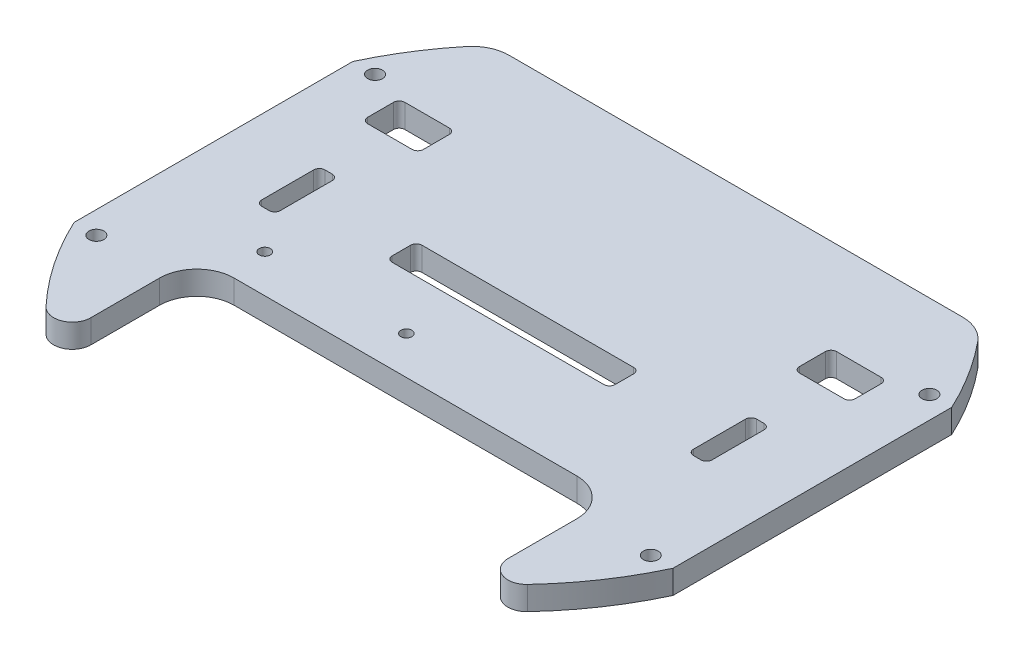
SolidWorks part; units mm, degrees
ref_plane "Front Plane" through (0, 0, 0) normal (0, 0, 1) x (1, 0, 0)
ref_plane "Top Plane" through (0, 0, 0) normal (0, 1, 0) x (1, 0, 0)
ref_plane "Right Plane" through (0, 0, 0) normal (1, 0, 0) x (0, 0, -1)
sketch "Sketch1" plane through (0, 0, 0) normal (0, 1, 0) x (1, 0, 0)
  line L0 (-80.6037, 37.5) -> (-80.6037, -37.5)
  line L1 (0, -88.9) -> (0, 88.9) construction
  line L2 (80.6037, 37.5) -> (80.6037, -37.5)
  arc A0 (-80.6037, -37.5) -> (80.6037, -37.5) centre (0, 0) ccw
  arc A1 (80.6037, 37.5) -> (-80.6037, 37.5) centre (0, 0) ccw
  dimension "D1" = 177.8
  dimension "D2" = 75
extrude "Main Body" add sketch "Sketch1" along normal blind 6.35
sketch "Sketch2" plane through (0, 6.35, 0) normal (0, 1, 0) x (1, 0, 0)
  line L0 (0, 88.9) -> (0, -88.9) construction
  line L1 (36.5, 69.85) -> (-21.5, 69.85) construction
  line L2 (36.5, 69.85) -> (36.5, 20.85) construction
  line L3 (36.5, 20.85) -> (-21.5, 20.85) construction
  line L4 (-21.5, 69.85) -> (-21.5, 20.85) construction
  line L5 (36.5, 69.85) -> (-21.5, 20.85) construction
  line L6 (36.5, 20.85) -> (-21.5, 69.85) construction
  line L7 (32.5, 20.85) -> (32.5, 69.85) construction
  line L8 (-25.5, 20.85) -> (-25.5, 69.85) construction
  circle A0 centre (36.5, 69.85) radius 1.524
  circle A1 centre (36.5, 20.85) radius 1.524
  circle A2 centre (-21.5, 20.85) radius 1.524
  circle A3 centre (-21.5, 69.85) radius 1.524
  arc A4 (-80.6037, -37.5) -> (80.6037, -37.5) centre (0, 0) ccw construction
  arc A5 (80.6037, 37.5) -> (-80.6037, 37.5) centre (0, 0) ccw construction
  circle A6 centre (32.5, 20.85) radius 1.1
  circle A7 centre (-25.5, 20.85) radius 1.1
  circle A8 centre (32.5, 69.85) radius 1.1
  circle A9 centre (-25.5, 69.85) radius 1.1
  point P0 (7.5, 45.35)
  point P11 (0, 88.9)
  dimension "D3" = 3.048
  dimension "D6" = 2.2
  dimension "D1" = 58
  dimension "D2" = 49
  dimension "D4" = 19.05
  dimension "D5" = 15
  dimension "D7" = 4
  dimension "D8" = 4
sketch "Sketch3" plane through (0, 6.35, 0) normal (0, 1, 0) x (1, 0, 0)
  line L0 (-80.6037, 0) -> (80.6037, 0) construction
  line L1 (-80.6037, 37.5) -> (-80.6037, -37.5) construction
  line L2 (80.6037, -37.5) -> (80.6037, 37.5) construction
  line L3 (-74.3537, -9) -> (-74.3537, 9) construction
  line L4 (0, -88.9) -> (0, 88.9) construction
  line L5 (74.3537, -9) -> (74.3537, 9) construction
  circle A0 centre (-74.3537, 9) radius 1.143
  circle A1 centre (-74.3537, -9) radius 1.143
  arc A2 (-80.6037, -37.5) -> (80.6037, -37.5) centre (0, 0) ccw construction
  arc A3 (80.6037, 37.5) -> (-80.6037, 37.5) centre (0, 0) ccw construction
  circle A4 centre (74.3537, 9) radius 1.143
  circle A5 centre (74.3537, -9) radius 1.143
  point P10 (-74.3537, 0)
  point P19 (74.3537, 0)
  dimension "D1" = 6.25
  dimension "D2" = 2.286
  dimension "D3" = 18
sketch "Sketch4" plane through (0, 6.35, 0) normal (0, 1, 0) x (1, 0, 0)
  line L0 (0, -88.9) -> (0, 88.9) construction
  line L1 (-7.747, 78.9) -> (7.747, 78.9) construction
  arc A0 (-80.6037, -37.5) -> (80.6037, -37.5) centre (0, 0) ccw construction
  arc A1 (80.6037, 37.5) -> (-80.6037, 37.5) centre (0, 0) ccw construction
  circle A2 centre (-7.747, 78.9) radius 1.524
  circle A3 centre (7.747, 78.9) radius 1.524
  point P10 (0, 78.9)
  dimension "D1" = 3.048
  dimension "D2" = 15.494
  dimension "D3" = 10
sketch "Sketch5" plane through (0, 6.35, 0) normal (0, 1, 0) x (1, 0, 0)
  line L0 (0, -88.9) -> (0, 88.9) construction
  line L1 (29.21, -82.5485) -> (29.21, 0.1133) construction
  line L2 (29.21, -24.4861) -> (50029.21, -24.4861) construction
  line L3 (29.21, -28.2961) -> (56.134, -28.2961) construction
  line L4 (29.21, -28.2961) -> (29.21, -68.9361) construction
  line L5 (29.21, -68.9361) -> (56.134, -68.9361) construction
  line L6 (56.134, -28.2961) -> (56.134, -68.9361) construction
  line L7 (29.21, -72.7461) -> (50029.21, -72.7461) construction
  line L8 (29.21, -28.2961) -> (29.21, -24.4861) construction
  line L9 (29.21, -68.9361) -> (29.21, -72.7461) construction
  line L10 (35.56, -24.4861) -> (35.56, -72.7461) construction
  arc A0 (-80.6037, -37.5) -> (80.6037, -37.5) centre (0, 0) ccw construction
  arc A1 (80.6037, 37.5) -> (-80.6037, 37.5) centre (0, 0) ccw construction
  circle A2 centre (35.56, -24.4861) radius 1.524
  circle A3 centre (35.56, -72.7461) radius 1.524
  dimension "D4" = 3.048
  dimension "D1" = 29.21
  dimension "D2" = 40.64
  dimension "D3" = 26.924
  dimension "D5" = 6.35
  dimension "D6" = 48.26
sketch "Sketch6" plane through (0, 6.35, 0) normal (0, 1, 0) x (1, 0, 0)
  line L0 (0, -88.1692) -> (0, -5.66) construction
  line L2 (-26.543, -75.692) -> (26.543, -75.692) construction
  line L3 (-26.543, -75.692) -> (-26.543, -63.5) construction
  line L4 (-26.543, -63.5) -> (26.543, -63.5) construction
  line L5 (26.543, -75.692) -> (26.543, -63.5) construction
  line L6 (-26.543, -75.692) -> (26.543, -63.5) construction
  line L7 (-26.543, -63.5) -> (26.543, -75.692) construction
  circle A0 centre (-12.7, -69.596) radius 1.524
  circle A1 centre (12.7, -69.596) radius 1.524
  point P1 (0, -69.596)
  dimension "D4" = 3.048
  dimension "D1" = 63.5
  dimension "D2" = 12.192
  dimension "D3" = 53.086
  dimension "D5" = 25.4
  dimension "D6" = 12.7
extrude "Front IR" cut sketch "Sketch6" against normal through all
sketch "Sketch8" plane through (0, 6.35, 0) normal (0, 1, 0) x (1, 0, 0)
  line L0 (0, 0) -> (0, 88.9) construction
  line L1 (-80.6037, 37.5) -> (-80.6037, -37.5) construction
  line L2 (-80.6037, -29.88) -> (80.6037, -29.88) construction
  line L3 (80.6037, -37.5) -> (80.6037, 37.5) construction
  line L4 (-80.6037, 23.206) -> (80.6037, 23.206) construction
  line L5 (0, 23.206) -> (0, -29.88) construction
  line L6 (0, -29.88) -> (0, -3.337) construction
  line L7 (-63.5, -37.5) -> (63.5, -37.5) construction
  circle A1 centre (-63.5, -37.5) radius 1.524
  circle A2 centre (-63.5, -50.2) radius 1.524
  circle A3 centre (63.5, -50.2) radius 1.524
  circle A4 centre (63.5, -37.5) radius 1.524
  dimension "D3" = 3.048
  dimension "D1" = 53.086
  dimension "D2" = 7.62
  dimension "D4" = 12.7
  dimension "D5" = 63.5
  dimension "D6" = 7.62
sketch "Sketch10" plane through (0, 6.35, 0) normal (0, 1, 0) x (1, 0, 0)
  line L0 (0, -88.9) -> (0, 0) construction
  line L1 (19.05, -101.854) -> (19.05, -75.946)
  line L2 (19.05, -101.854) -> (-19.05, -101.854)
  line L3 (19.05, -75.946) -> (-19.05, -75.946)
  line L4 (-19.05, -101.854) -> (-19.05, -75.946)
  line L5 (19.05, -101.854) -> (-19.05, -75.946) construction
  line L6 (19.05, -75.946) -> (-19.05, -101.854) construction
  arc A0 (-80.6037, -37.5) -> (80.6037, -37.5) centre (0, 0) ccw construction
  circle A1 centre (-12.7, -69.596) radius 1.524 construction
  dimension "D2" = 6.35
  dimension "D1" = 38.1
extrude "Grabber slot" cut sketch "Sketch10" against normal through all
sketch "Sketch11" plane through (0, 6.35, 0) normal (0, 1, 0) x (1, 0, 0)
  line L0 (0, 88.9) -> (0, -75.946) construction
  line L1 (19.05, -75.946) -> (-19.05, -75.946) construction
  line L2 (80.6037, 0) -> (-80.6037, 0) construction
  line L3 (80.6037, -37.5) -> (80.6037, 37.5) construction
  line L4 (-80.6037, 37.5) -> (-80.6037, -37.5) construction
  line L5 (-60.6037, 8.5) -> (-55.6037, 8.5)
  line L6 (30, -4) -> (-30, -4)
  line L7 (30, -4) -> (30, 4)
  line L8 (30, 4) -> (-30, 4)
  line L9 (-30, -4) -> (-30, 4)
  line L10 (30, -4) -> (-30, 4) construction
  line L11 (30, 4) -> (-30, -4) construction
  line L12 (60.6037, -8.5) -> (55.6037, -8.5)
  line L13 (60.6037, -8.5) -> (60.6037, 8.5)
  line L14 (60.6037, 8.5) -> (55.6037, 8.5)
  line L15 (55.6037, -8.5) -> (55.6037, 8.5)
  line L16 (60.6037, -8.5) -> (55.6037, 8.5) construction
  line L17 (60.6037, 8.5) -> (55.6037, -8.5) construction
  line L18 (-55.6037, -8.5) -> (-55.6037, 8.5)
  line L19 (-60.6037, -8.5) -> (-55.6037, -8.5)
  line L20 (-60.6037, -8.5) -> (-60.6037, 8.5)
  line L21 (-58.1037, 8.5) -> (-58.1037, 67.2842) construction
  line L22 (58.1037, 8.5) -> (58.1037, 67.2842) construction
  line L23 (50.6037, 35) -> (50.6037, 25)
  line L24 (-65.6037, 35) -> (-50.6037, 35)
  line L25 (-65.6037, 35) -> (-65.6037, 25)
  line L26 (-65.6037, 25) -> (-50.6037, 25)
  line L27 (-50.6037, 35) -> (-50.6037, 25)
  line L28 (-65.6037, 35) -> (-50.6037, 25) construction
  line L29 (-65.6037, 25) -> (-50.6037, 35) construction
  line L30 (65.6037, 35) -> (50.6037, 35)
  line L31 (65.6037, 35) -> (65.6037, 25)
  line L32 (65.6037, 25) -> (50.6037, 25)
  arc A0 (80.6037, 37.5) -> (-80.6037, 37.5) centre (0, 0) ccw construction
  point P13 (0, 0)
  point P19 (58.1037, 0)
  point P32 (-58.1037, 30)
  dimension "D3" = 20
  dimension "D1" = 8
  dimension "D2" = 60
  dimension "D4" = 17
  dimension "D5" = 5
  dimension "D6" = 15
  dimension "D7" = 10
  dimension "D8" = 30
extrude "Wire slots" cut sketch "Sketch11" against normal through all
sketch "Sketch13" plane through (0, 6.35, 0) normal (0, 1, 0) x (1, 0, 0)
  line L0 (0, 88.9) -> (0, -75.946) construction
  line L1 (19.05, -75.946) -> (-19.05, -75.946) construction
  line L2 (80.6037, 0) -> (-80.6037, 0) construction
  line L3 (80.6037, -37.5) -> (80.6037, 37.5) construction
  line L4 (-80.6037, 37.5) -> (-80.6037, -37.5) construction
  line L5 (80.6037, -37.5) -> (-80.6037, -37.5) construction
  line L6 (80.6037, 37.5) -> (-80.6037, 37.5) construction
  line L8 (74.6037, 37.5) -> (-74.6037, 37.5) construction
  line L9 (74.6037, 37.5) -> (74.6037, -37.5) construction
  line L10 (74.6037, -37.5) -> (-74.6037, -37.5) construction
  line L11 (-74.6037, 37.5) -> (-74.6037, -37.5) construction
  line L12 (74.6037, 37.5) -> (-74.6037, -37.5) construction
  line L13 (74.6037, -37.5) -> (-74.6037, 37.5) construction
  arc A0 (80.6037, 37.5) -> (-80.6037, 37.5) centre (0, 0) ccw construction
  circle A1 centre (74.6037, -37.5) radius 2
  circle A2 centre (-74.6037, -37.5) radius 2
  circle A3 centre (74.6037, 37.5) radius 2
  circle A4 centre (-74.6037, 37.5) radius 2
  point P21 (0, 0)
  dimension "D2" = 4
  dimension "D1" = 6
extrude "2nd level" cut sketch "Sketch13" against normal through all
sketch "Sketch14" plane through (0, 6.35, 0) normal (0, 1, 0) x (1, 0, 0)
  line L0 (56.134, -68.9361) -> (56.134, -28.9361)
  line L1 (56.134, -28.9361) -> (-56.134, -28.9361)
  line L2 (-56.134, -28.9361) -> (-56.134, -68.9361)
  line L3 (19.05, -86.8349) -> (19.05, -75.946) construction
  line L4 (19.05, -75.946) -> (-19.05, -75.946) construction
  line L5 (-19.05, -75.946) -> (-19.05, -86.8349) construction
  line L6 (19.05, -86.8349) -> (19.05, -75.946)
  line L7 (19.05, -75.946) -> (-19.05, -75.946)
  line L8 (-19.05, -75.946) -> (-19.05, -86.8349)
  arc A0 (-80.6037, -37.5) -> (-19.05, -86.8349) centre (0, 0) ccw construction
  arc A1 (19.05, -86.8349) -> (80.6037, -37.5) centre (0, 0) ccw construction
  arc A2 (19.05, -86.8349) -> (56.134, -68.9361) centre (0, 0) ccw
  arc A3 (-56.134, -68.9361) -> (-19.05, -86.8349) centre (0, 0) ccw
  dimension "D1" = 40
extrude "Cut-Extrude1" cut sketch "Sketch14" against normal through all
fillet "Fillet1" radius 5 2 edges at (-56.134, 3.175, 68.9361) (56.134, 3.175, 68.9361)
fillet "Fillet2" radius 10 2 edges at (-56.134, 3.175, 28.9361) (56.134, 3.175, 28.9361)
sketch "Sketch16" plane through (0, 6.35, 0) normal (0, 1, 0) x (1, 0, 0)
  line L0 (65.5989, 60) -> (-65.5989, 60)
  arc A0 (80.6037, 37.5) -> (-80.6037, 37.5) centre (0, 0) ccw construction
  arc A1 (65.5989, 60) -> (-65.5989, 60) centre (0, 0) ccw
  dimension "D1" = 60
extrude "Cut-Extrude2" cut sketch "Sketch16" against normal blind 10
fillet "Fillet3" radius 10 2 edges at (-65.5989, 3.175, -60) (65.5989, 3.175, -60)
fillet "Fillet4" radius 1.5 20 edges at (-60.6037, 3.175, 8.5) (-60.6037, 3.175, -8.5) (-55.6037, 3.175, 8.5) (-55.6037, 3.175, -8.5) (55.6037, 3.175, 8.5) (55.6037, 3.175, -8.5) (60.6037, 3.175, -8.5) (60.6037, 3.175, 8.5) (30, 3.175, 4) (30, 3.175, -4) (-30, 3.175, 4) (-30, 3.175, -4) (50.6037, 3.175, -25) (50.6037, 3.175, -35) (65.6037, 3.175, -35) (65.6037, 3.175, -25) (-50.6037, 3.175, -25) (-65.6037, 3.175, -25) (-50.6037, 3.175, -35) (-65.6037, 3.175, -35)
sketch "Sketch17" plane through (0, 6.35, 0) normal (0, 1, 0) x (1, 0, 0)
  line L0 (-80.6037, -18.6787) -> (80.6037, -18.6787) construction
  line L1 (-80.6037, 37.5) -> (-80.6037, -37.5) construction
  line L2 (80.6037, -37.5) -> (80.6037, 37.5) construction
  line L3 (0, 88.9) -> (0, -88.9) construction
  circle A0 centre (-48.1, -18.6787) radius 1.5
  circle A1 centre (-10, -18.6787) radius 1.5
  dimension "D2" = 3
  dimension "D1" = 38.1
  dimension "D3" = 10
extrude "Cut-Extrude3" cut sketch "Sketch17" against normal through all
